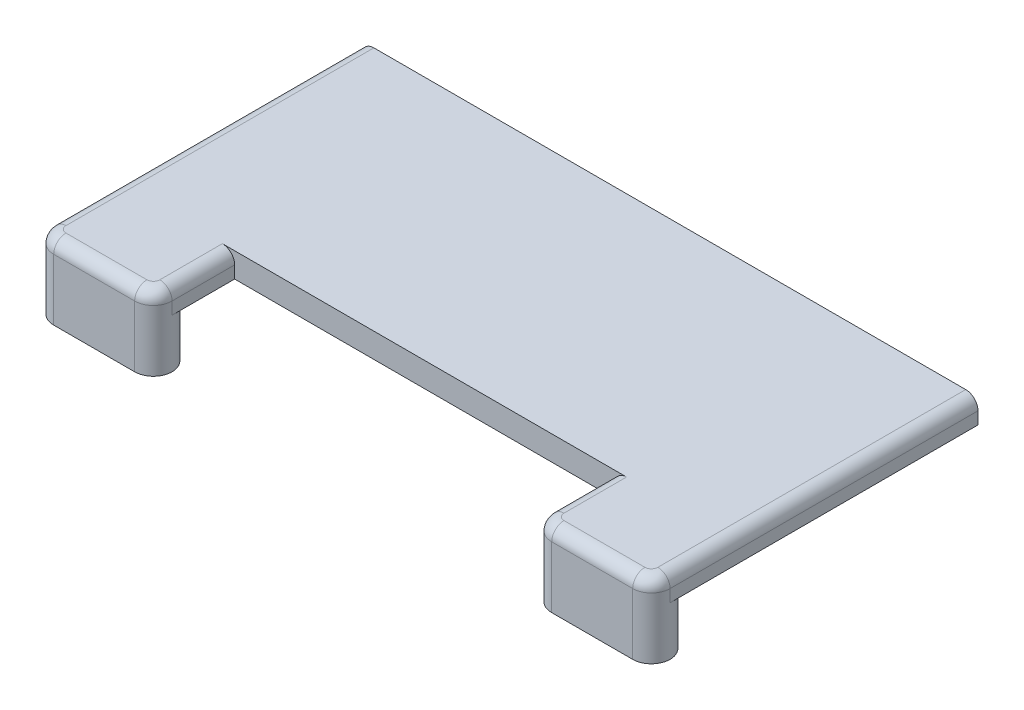
SolidWorks part; units mm, degrees
ref_plane "Front" through (0, 0, 0) normal (0, 0, 1) x (1, 0, 0)
ref_plane "Top" through (0, 0, 0) normal (0, 1, 0) x (1, 0, 0)
ref_plane "Right" through (0, 0, 0) normal (1, 0, 0) x (0, 0, -1)
sketch "Sketch1" plane through (0, 0, 0) normal (0, 1, 0) x (1, 0, 0)
  line L0 (0, -55) -> (0, 55) construction
  line L5 (-23.6, 10.5423) -> (-17, 10.5423)
  line L6 (-23.6, 7.4923) -> (-17, 7.4923)
  line L7 (23.6, 7.4923) -> (17, 7.4923)
  line L8 (23.6, 10.5423) -> (17, 10.5423)
  arc A0 (-23.6, 10.5423) -> (-23.6, 7.4923) centre (-23.6, 9.0173) ccw
  arc A1 (-17, 7.4923) -> (-17, 10.5423) centre (-17, 9.0173) ccw
  arc A2 (23.6, 10.5423) -> (23.6, 7.4923) centre (23.6, 9.0173) cw
  arc A3 (17, 7.4923) -> (17, 10.5423) centre (17, 9.0173) cw
  dimension "D1" = 3.05
  dimension "D2" = 6.6
  dimension "D3" = 17
extrude "Boss-Extrude1" add sketch "Sketch1" along normal blind 4
sketch "Sketch3" plane through (0, 4, 0) normal (0, 1, 0) x (1, 0, 0)
  line L1 (17, 7.4923) -> (23.6, 7.4923) construction
  line L2 (-23.6, 7.4923) -> (-17, 7.4923) construction
  line L5 (17, 7.4923) -> (23.6, 7.4923)
  line L6 (-23.6, 7.4923) -> (-17, 7.4923)
  line L8 (-25.125, 9.0173) -> (-25.125, 17.3059)
  line L9 (-15.475, 14.1173) -> (15.475, 14.1173)
  line L11 (-25.125, 34.1173) -> (25.125, 34.1173)
  line L13 (-15.475, 9.0173) -> (-15.475, 14.1173)
  line L14 (0, -55) -> (0, 55) construction
  line L15 (23.6, 7.4923) -> (17, 7.4923)
  line L16 (15.475, 9.0173) -> (15.475, 14.1173)
  line L17 (15.475, 14.1173) -> (-15.475, 14.1173)
  line L18 (-25.125, 17.3059) -> (-25.125, 34.1173)
  line L19 (25.125, 34.1173) -> (25.125, 17.3059)
  line L20 (25.125, 9.0173) -> (25.125, 17.3059)
  arc A0 (23.6, 7.4923) -> (23.6, 10.5423) centre (23.6, 9.0173) ccw construction
  arc A1 (17, 10.5423) -> (17, 7.4923) centre (17, 9.0173) ccw construction
  arc A2 (-23.6, 10.5423) -> (-23.6, 7.4923) centre (-23.6, 9.0173) ccw construction
  arc A3 (-17, 7.4923) -> (-17, 10.5423) centre (-17, 9.0173) ccw construction
  arc A4 (23.6, 7.4923) -> (25.125, 9.0173) centre (23.6, 9.0173) ccw
  arc A5 (15.475, 9.0173) -> (17, 7.4923) centre (17, 9.0173) ccw
  arc A6 (-25.125, 9.0173) -> (-23.6, 7.4923) centre (-23.6, 9.0173) ccw
  arc A7 (-17, 7.4923) -> (-15.475, 9.0173) centre (-17, 9.0173) ccw
  arc A8 (25.125, 9.0173) -> (23.6, 7.4923) centre (23.6, 9.0173) cw
  arc A9 (17, 7.4923) -> (15.475, 9.0173) centre (17, 9.0173) cw
  arc M5 (-23.6, 10.5423) -> (-23.6, 7.4923) centre (-23.6, 9.0173) ccw
  line M6 (-23.6, 7.4923) -> (-17, 7.4923)
  arc M7 (-17, 7.4923) -> (-17, 10.5423) centre (-17, 9.0173) ccw
  line M8 (-17, 10.5423) -> (-23.6, 10.5423)
  dimension "D1" = 5.1
  dimension "D2" = 20
extrude "Boss-Extrude3" add sketch "Sketch3" along normal blind 2 contours L16 A5 L5 A4 L20 L19 L11 L18 L8 L13 L9 M5 M8 M7 | M8 M5 M6 M7 region at (0.5047, 4, -22.9796) region at (-20.3, 4, -9.0173)
fillet "Fillet2" radius 1 10 edges at (-25.125, 6, -21.5673) (-24.6783, 6, -7.9389) (-15.475, 6, -11.5673) (-15.9217, 6, -7.9389) (15.475, 6, -11.5673) (15.9217, 6, -7.9389) (25.125, 6, -21.5673) (24.6783, 6, -7.9389) (-20.3, 6, -7.4923) (20.3, 6, -7.4923)
